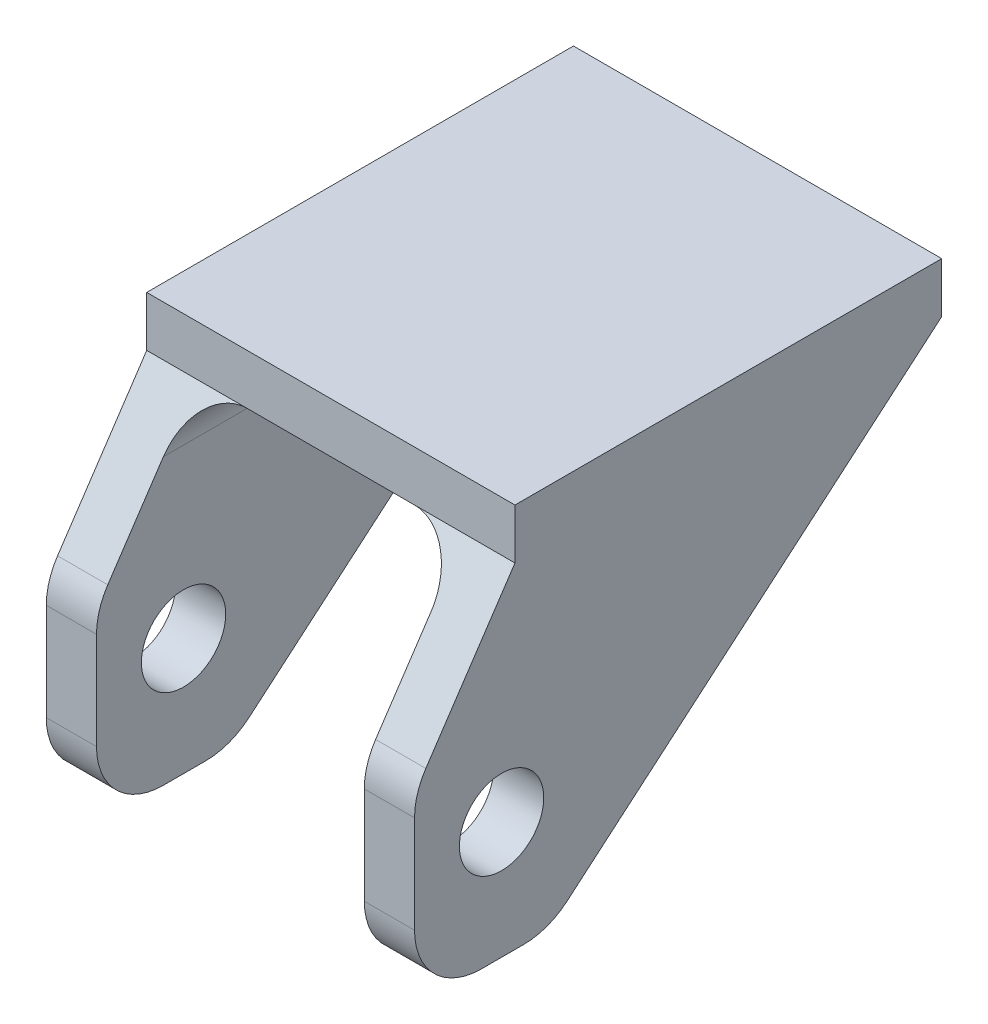
SolidWorks part; units mm, degrees
note: The reader was unsure of these and kept them because the rebuilt part matched: shared geometry of "Sketch1<3>".
material "6061-T6 (SS)"
ref_plane "Front Plane" through (0, 0, 0) normal (0, 0, 1) x (1, 0, 0)
ref_plane "Top Plane" through (0, 0, 0) normal (0, 1, 0) x (1, 0, 0)
ref_plane "Right Plane" through (0, 0, 0) normal (1, 0, 0) x (0, 0, -1)
sketch "Sketch1" plane through (0, 0, 0) normal (0, 1, 0) x (1, 0, 0)
  line L1 (-12.7, -25) -> (12.7, -25)
  line L2 (-12.7, -25) -> (-12.7, 25)
  line L3 (-12.7, 25) -> (12.7, 25)
  line L4 (12.7, -25) -> (12.7, 25)
  line L5 (-12.7, -25) -> (12.7, 25) construction
  line L6 (-12.7, 25) -> (12.7, -25) construction
  line L7 (12.7, 25) -> (17.4625, 25)
  line L8 (12.7, 25) -> (12.7, -25)
  line L9 (12.7, -25) -> (17.4625, -25)
  line L10 (17.4625, 25) -> (17.4625, -25)
  line L11 (-12.7, 25) -> (-17.4625, 25)
  line L12 (-12.7, 25) -> (-12.7, -25)
  line L13 (-12.7, -25) -> (-17.4625, -25)
  line L14 (-17.4625, 25) -> (-17.4625, -25)
  point P0 (0, 0)
  dimension "D1" = 25.4
  dimension "D2" = 50
  dimension "D3" = 4.7625
  dimension "D4" = 4.7625
extrude "Boss-Extrude1" add sketch "Sketch1" along normal blind 4.7625 contours L11 L14 L13 L2 | L1 L4 L3 L2 | L10 L7 L4 L9
extrude "Boss-Extrude2" add sketch "Sketch1<3>" against normal blind 31.75 contours L11 L14 L13 L2 | L10 L7 L4 L9
sketch "Sketch1<3>" plane through (0, 0, 0) normal (0, 1, 0) x (1, 0, 0) same geometry as "Sketch1"
sketch "Sketch3" plane through (17.4625, 0, 0) normal (1, 0, 0) x (0, 0, -1)
  line L0 (25, 0) -> (-12.3, -31.75)
  line L1 (25, 0) -> (-25, 0) construction
  line L2 (-12.3, -31.75) -> (-25, -31.75)
  line L3 (-25, -14.2476) -> (-15.475, 0)
  line L4 (-25, 4.7625) -> (-25, -31.75)
  line L5 (-25, -31.75) -> (25, -31.75)
  line L6 (25, -31.75) -> (25, 4.7625)
  line L7 (25, 4.7625) -> (-25, 4.7625)
  line L8 (-25, 4.7625) -> (-25, -31.75)
  line L9 (-25, -31.75) -> (25, -31.75)
  line L10 (25, -31.75) -> (25, 4.7625)
  line L11 (25, 4.7625) -> (-25, 4.7625)
  line L12 (-25, 0) -> (-25, -31.75)
  line L13 (-15.475, 0) -> (-15.475, 4.7625)
  line L14 (-25, 4.7625) -> (-25, -31.75) construction
  circle A0 centre (-16.745, -20.6375) radius 4
  line M10 (-25, 4.7625) -> (-25, -31.75)
  line M11 (-25, -31.75) -> (25, -31.75)
  line M12 (25, -31.75) -> (25, 4.7625)
  dimension "D4" = 8
  dimension "D2" = 10.414
  dimension "D3" = 12.7
  dimension "D5" = 25.4
  dimension "D6" = 9.525
  dimension "D7" = 1.27
  dimension "D1" = 0
extrude "Cut-Extrude1" cut sketch "Sketch3" against normal through all contours L0 M12 M11 | L3 L13 L11 L8 M10 | A0
fillet "Fillet1" radius 6.35 6 edges at (-15.0812, -31.75, 25) (15.0813, -31.75, 25) (15.0813, -31.75, 12.3) (-15.0812, -31.75, 12.3) (15.0813, -14.2476, 25) (-15.0812, -14.2476, 25)
fillet "Fillet2" radius 4.7625 2 edges at (12.7, 0, -4.7625) (-12.7, 0, -4.7625)
